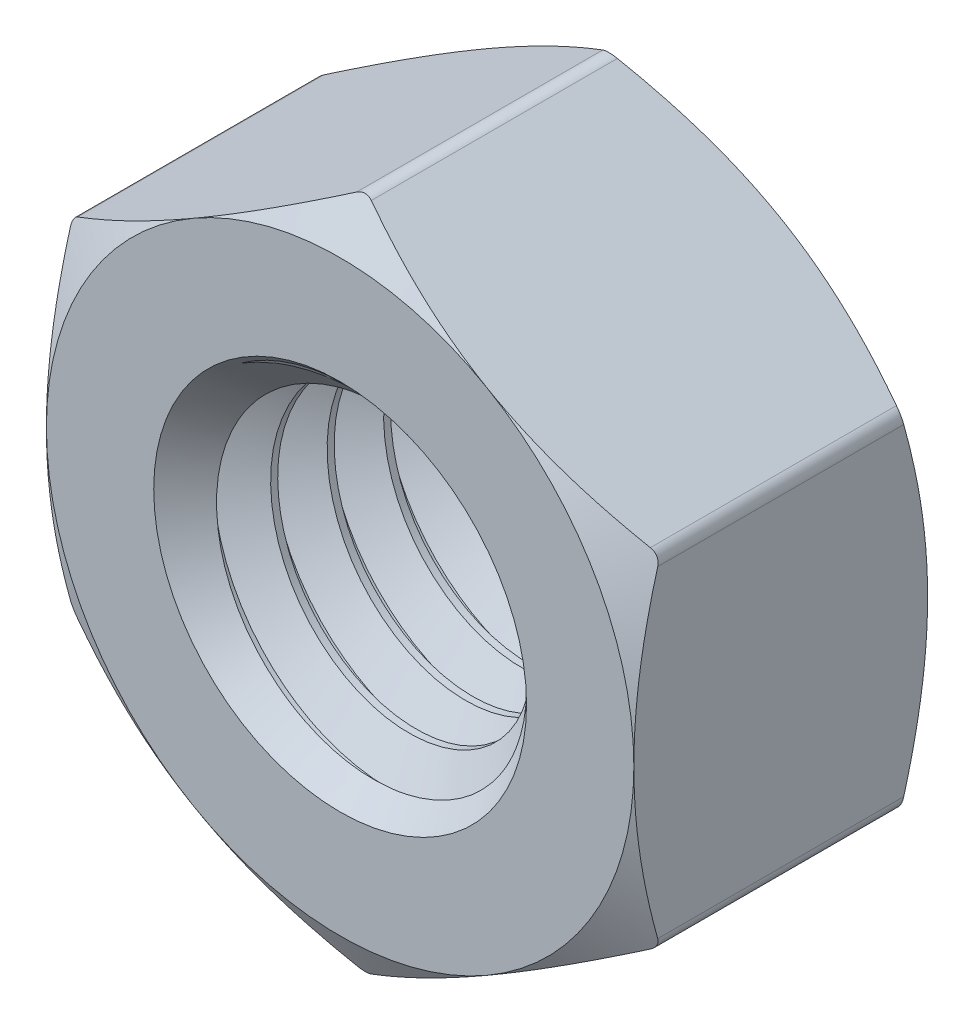
SolidWorks part; units mm, degrees
ref_plane "Front" through (0, 0, 0) normal (0, 0, 1) x (1, 0, 0)
ref_plane "Top" through (0, 0, 0) normal (0, 1, 0) x (1, 0, 0)
ref_plane "Right" through (0, 0, 0) normal (1, 0, 0) x (0, 0, -1)
sketch "Sketch1" plane through (0, 0, 0) normal (0, 0, 1) x (1, 0, 0)
  line L0 (0, 4) -> (0, 2.75) construction
  line L1 (-6.5, 3.7528) -> (-6.5, -3.7528)
  line L2 (-6.5, -3.7528) -> (0, -7.5056)
  line L3 (0, -7.5056) -> (6.5, -3.7528)
  line L4 (6.5, -3.7528) -> (6.5, 3.7528)
  line L5 (6.5, 3.7528) -> (0, 7.5056)
  line L6 (0, 7.5056) -> (-6.5, 3.7528)
  circle A0 centre (0, 0) radius 6.5 construction
  circle A1 centre (0, 0) radius 4 construction
  point P10 (0, 4)
  dimension "Width" = 13
  dimension "Thread Size" = 8
  dimension "Thread Pitch" = 1.25
sketch "Sketch2" plane through (0, 0, 0) normal (1, 0, 0) x (0, 0, -1)
  line L0 (-3.25, 0) -> (3.25, 0) construction
  line L1 (-3.25, 7.5056) -> (3.25, 7.5056) construction
  dimension "Height" = 6.5
sketch "Sketch15" plane through (0, 0, 0) normal (0, 0, 1) x (1, 0, 0)
  line L1 (0, 7.5056) -> (-6.5, 3.7528)
  line L2 (-6.5, 3.7528) -> (-6.5, -3.7528)
  line L3 (-6.5, -3.7528) -> (0, -7.5056)
  line L4 (0, -7.5056) -> (6.5, -3.7528)
  line L5 (6.5, -3.7528) -> (6.5, 3.7528)
  line L6 (6.5, 3.7528) -> (0, 7.5056)
  circle A0 centre (0, 0) radius 6.5 construction
extrude "Boss-Extrude2" add sketch "Sketch15" along normal mid plane 6.5
sketch "Sketch16" plane through (0, 0, 0) normal (0, 0, 1) x (1, 0, 0)
  circle A0 centre (0, 0) radius 4 construction
  circle A1 centre (0, 0) radius 4
sketch "Sketch4" plane through (0, 0, -3.25) normal (0, 0, -1) x (-1, 0, 0)
  circle A0 centre (0, 0) radius 4 construction
  circle A1 centre (0, 0) radius 4
extrude "Cut-Extrude4" cut sketch "Sketch16" against normal through all both and the other way through all
sketch "Sketch7" plane through (0, 0, 3.25) normal (0, 0, 1) x (1, 0, 0)
  circle A0 centre (0, 0) radius 6.5 construction
  circle A1 centre (0, 0) radius 6.5
extrude "Cut-Extrude5" cut sketch "Sketch7" against normal through all draft 60 flip side to cut
mirror "Mirror4" about plane through (0, 0, 0) normal (0, 0, 1) of "Cut-Extrude5"
fillet "Fillet2" radius 0.325 6 edges at (-6.5, 3.7528, 0) (-6.5, -3.7528, 0) (0, -7.5056, 0) (6.5, -3.7528, 0) (6.5, 3.7528, 0) (0, 7.5056, 0)
sketch "Sketch8" plane through (0, 0, 3.25) normal (0, 0, 1) x (1, 0, 0)
  line L0 (1.0353, -3.8637) -> (0, 0) construction
  line L2 (0, 4) -> (0, 2.75) construction
  circle A0 centre (0, 0) radius 4 construction
  point P0 (1.0353, -3.8637)
  dimension "D1" = 15
sketch "Sketch13" plane through (0, 0, -3.25) normal (0, 0, -1) x (-1, 0, 0)
  circle A0 centre (0, 0) radius 4 construction
  circle A1 centre (0, 0) radius 4
extrude "Boss-Extrude1" add sketch "Sketch13" against normal up to surface (6.5 mm away) separate body up to face at (4, 0, 3.25)
curve "Helix/Spiral3" pitch 1.25 height 9 radius 4 centre (0, 0, -3.25) axis (0, 0, 1) start towards (0, 1, 0)
sketch "Sketch12" plane through (0, 0, 0) normal (1, 0, 0) x (0, 0, -1)
  line L0 (4.3438, 4) -> (3.25, 4)
  line L1 (4.3438, 4) -> (3.875, 3.1881)
  line L2 (3.875, 3.1881) -> (3.7188, 3.1881)
  line L3 (3.7188, 3.1881) -> (3.25, 4)
  line L4 (3.7969, 3.1881) -> (3.7969, 4) construction
  line L5 (3.4844, 3.5941) -> (4.1094, 3.5941) construction
  dimension "D1" = 60
  dimension "D2" = 0.1562
  dimension "D3" = 0.625
sweep "Cut-Sweep1" cut profiles "Sketch12" path "Helix/Spiral3" align with end faces yes
sketch "Sketch17" plane through (0, 0, 3.25) normal (0, 0, 1) x (1, 0, 0)
  circle A1 centre (0, 0) radius 4
  circle A2 centre (0, 0) radius 4
  dimension "D1" = 0
extrude "Boss-Extrude3" add sketch "Sketch17" against normal up to surface (6.5 mm away) up to face at (4, 0, -3.25)
combine bodies "Combine1" operation type subtract main body 127 bodies to subtract 118
sketch "Sketch10" plane through (0, 0, 3.25) normal (0, 0, 1) x (1, 0, 0)
  circle A0 centre (0, 0) radius 4 construction
  circle A1 centre (0, 0) radius 4 construction
  circle A2 centre (0, 0) radius 4.125
  dimension "D1" = 0.125
extrude "Cut-Extrude2" cut sketch "Sketch10" against normal through all draft 45
sketch "Sketch11" plane through (0, 0, -3.25) normal (0, 0, -1) x (-1, 0, 0)
  circle A1 centre (0, 0) radius 4.125 construction
  circle A2 centre (0, 0) radius 4.125
extrude "Cut-Extrude3" cut sketch "Sketch11" against normal through all draft 45
equation "\"D1\"= \"Height@Sketch2\""
equation "\"D3@Helix/Spiral3\"=\"Height@Sketch2\"+\"Thread Pitch@Sketch1\"*2"
equation "\"D4@Helix/Spiral3\"=\"Thread Pitch@Sketch1\""
equation "\"D2@Sketch12\" = \"D4@Helix/Spiral3\"*.125"
equation "\"D3@Sketch12\" = \"D4@Helix/Spiral3\"*.50"
equation "\"D1@Boss-Extrude2\"=\"Height@Sketch2\""
equation "\"D1@Fillet2\"=\"Width@Sketch1\"*0.025"
equation "\"D1@Sketch10\"=\"Thread Pitch@Sketch1\"*0.1"
